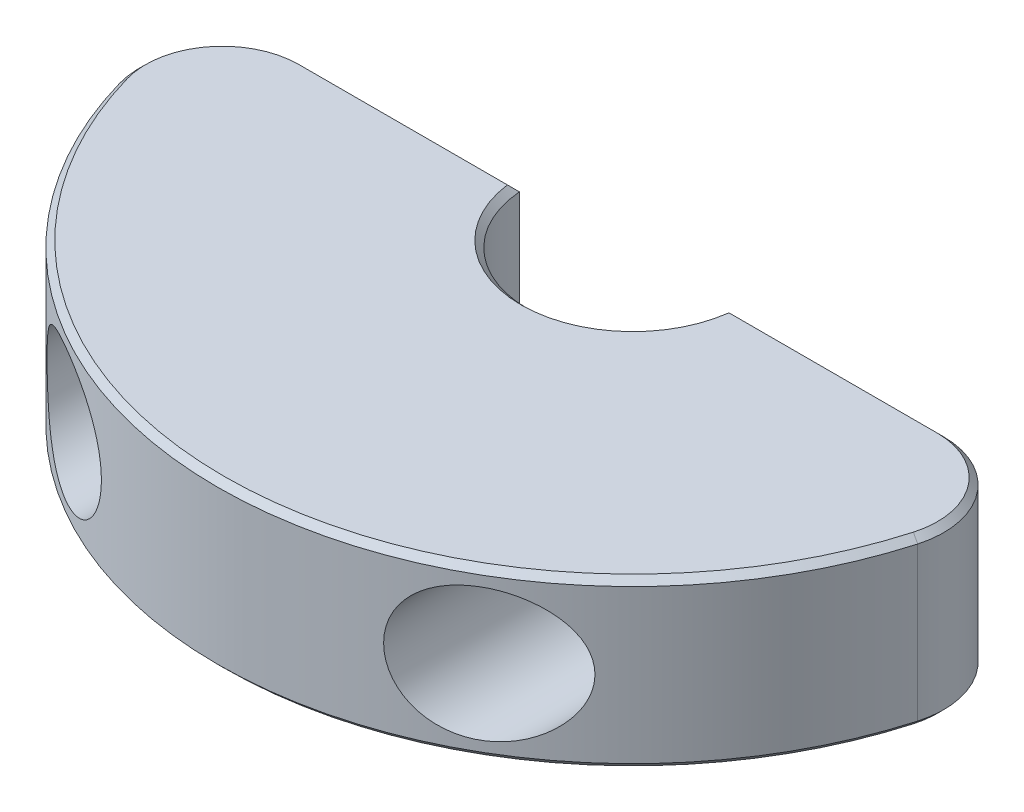
SolidWorks part; units mm, degrees
material "Nylon 101"
ref_plane "Front" through (0, 0, 0) normal (0, 0, 1) x (1, 0, 0)
ref_plane "Top" through (0, 0, 0) normal (0, 1, 0) x (1, 0, 0)
ref_plane "Right" through (0, 0, 0) normal (1, 0, 0) x (0, 0, -1)
sketch "Sketch1" plane through (0, 0, 0) normal (0, 1, 0) x (1, 0, 0)
  line L0 (-25, -50) -> (25, -50) construction
  line L1 (-15, 37.5) -> (15, 37.5) construction
  line L2 (0, -50) -> (0, 50) construction
  line L3 (-25, -50) -> (-25, 50)
  line L4 (25, -50) -> (25, 50)
  line L5 (25, 0) -> (0, 0) construction
  line L6 (25, 17) -> (97.2, 17)
  line L7 (25, 17) -> (25, -17)
  line L8 (25, -17) -> (97.2, -17)
  line L9 (97.2, 17) -> (97.2, -17)
  line L10 (-15, 37.5) -> (-15, -37.5) construction
  line L11 (-15, -37.5) -> (15, -37.5) construction
  line L12 (15, 37.5) -> (15, -37.5) construction
  line L13 (-25, -50.5) -> (25, -50.5)
  line L14 (-25, -49.5) -> (25, -49.5)
  line L15 (-25, 50.5) -> (25, 50.5)
  line L16 (-25, 49.5) -> (25, 49.5)
  circle A0 centre (0, 50) radius 6.35
  circle A1 centre (0, -50) radius 6.35
  arc A2 (-25, -50) -> (25, -50) centre (0, -50) ccw
  arc A3 (25, 50) -> (-25, 50) centre (0, 50) ccw
  circle A6 centre (-15, 37.5) radius 2.5
  circle A7 centre (-15, -37.5) radius 2.5
  circle A8 centre (15, -37.5) radius 2.5
  circle A9 centre (15, 37.5) radius 2.5
  point P8 (0, 0)
  point P24 (0, -37.5)
  dimension "D2" = 12.7
  dimension "D5" = 25
  dimension "D1" = 5
  dimension "D3" = 100
  dimension "D4" = 12.5
  dimension "D6" = 12.5
  dimension "D7" = 34
  dimension "D8" = 72.2
  dimension "D9" = 30
  dimension "D10" = 0.5
  dimension "D11" = 0.5
extrude "Boss-Extrude1" add sketch "Sketch1" along normal blind 10 contours L13 A2 A1 region at (0, 0, 61.3823)
fillet "Fillet1" radius 5 2 edges at (-24.995, 5, 50.5) (24.995, 5, 50.5)
sketch "Sketch2" plane through (0, 0, 50.5) normal (0, 0, -1) x (-1, 0, 0)
  line L0 (-12.5, 10) -> (-12.5, 0) construction
  line L1 (-6.3303, 10) -> (-19.2289, 10) construction
  line L2 (-6.3303, 0) -> (-19.2289, 0) construction
  line L3 (12.5, 10) -> (12.5, 0) construction
  line L4 (19.2289, 10) -> (6.3303, 10) construction
  line L5 (19.2289, 0) -> (6.3303, 0) construction
  line L6 (0, 0) -> (0, 2.7242) construction
  line L7 (-6.3303, 0) -> (6.3303, 0) construction
  circle A0 centre (-12.5, 5) radius 1.5
  circle A1 centre (12.5, 5) radius 1.5
  circle A2 centre (-12.5, 5) radius 4
  circle A3 centre (12.5, 5) radius 4
  dimension "D1" = 3
  dimension "D3" = 8
  dimension "D2" = 12.5
extrude "Cut-Extrude1" cut sketch "Sketch2" against normal through all contours A0 | A1 region at (12.5, 5, 50.5) region at (-12.5, 5, 50.5)
extrude "Cut-Extrude2" cut sketch "Sketch2<3>" against normal through all from offset 10 contours A2 A0 | A3 A1 region at (16.3869, 5, 50.5) region at (-8.6131, 5, 50.5) offset against normal yes
sketch "Sketch2<3>" plane through (0, 0, 50.5) normal (0, 0, -1) x (-1, 0, 0) same geometry as "Sketch2"
chamfer "Chamfer1" distance 0.381 angle 45 16 edges at (-14, 5, 50.5) (-14, 5, 60.5) (11, 5, 50.5) (11, 5, 60.5) (0, 10, 56.35) (-12.7796, 10, 50.5) (12.7796, 10, 50.5) (-23.2211, 10, 52.4896) (23.2211, 10, 52.4896) (0, 10, 75) (0, 0, 56.35) (-12.7796, 0, 50.5) (12.7796, 0, 50.5) (-23.2211, 0, 52.4896) (23.2211, 0, 52.4896) (0, 0, 75)
